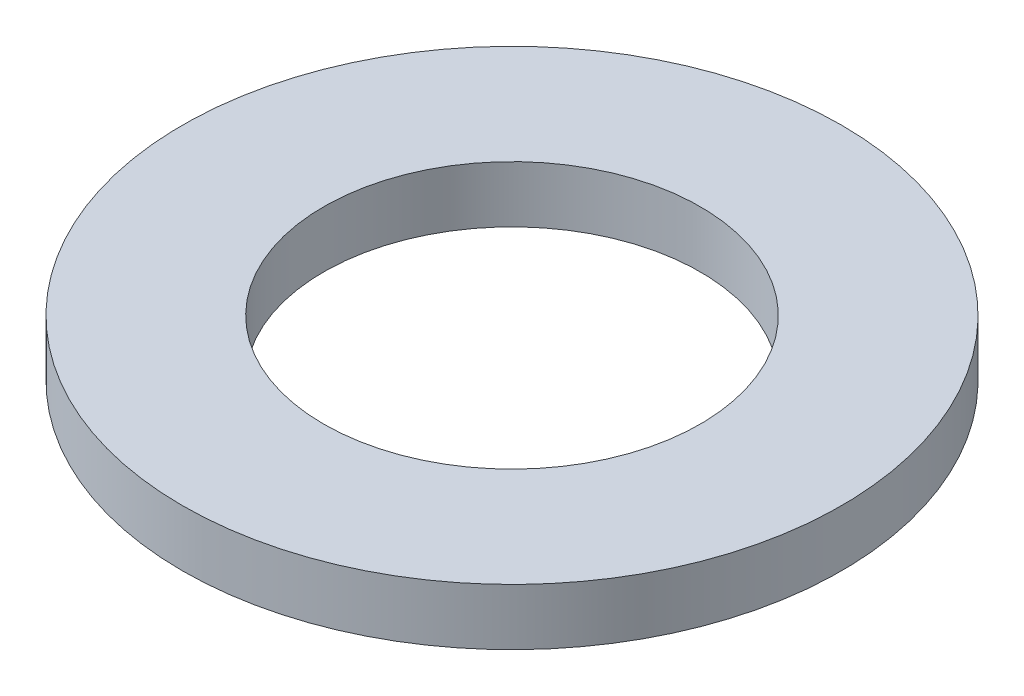
SolidWorks part; units mm, degrees
ref_plane "Front Plane" through (0, 0, 0) normal (0, 0, 1) x (1, 0, 0)
ref_plane "Top Plane" through (0, 0, 0) normal (0, 1, 0) x (1, 0, 0)
ref_plane "Right Plane" through (0, 0, 0) normal (1, 0, 0) x (0, 0, -1)
sketch "Sketch1" plane through (0, 0, 0) normal (0, 1, 0) x (1, 0, 0)
  circle A0 centre (0, 0) radius 70
  dimension "FLANGE_OD" = 140
extrude "Boss-Extrude1" add sketch "Sketch1" along normal blind 12
sketch "Sketch2" plane through (0, 0, 0) normal (0, 1, 0) x (1, 0, 0)
  circle A0 centre (0, 0) radius 40
  dimension "BORE_D" = 80
extrude "Cut-Extrude1" cut sketch "Sketch2" along normal through all
sketch "Sketch3" plane through (0, 12, 0) normal (0, 1, 0) x (1, 0, 0)
  circle A0 centre (0, 0) radius 26.1062 construction
  circle A1 centre (-26.1062, 0) radius 2.8515
  dimension "BOLT_D" = 5.7031
  dimension "BOLT_PCD" = 52.2124
extrude "Cut-Extrude2" cut sketch "Sketch3" against normal blind 10.4554 rebuild error yes
pattern_circular "CirPattern1" count 4 over 360 rebuild error yes
